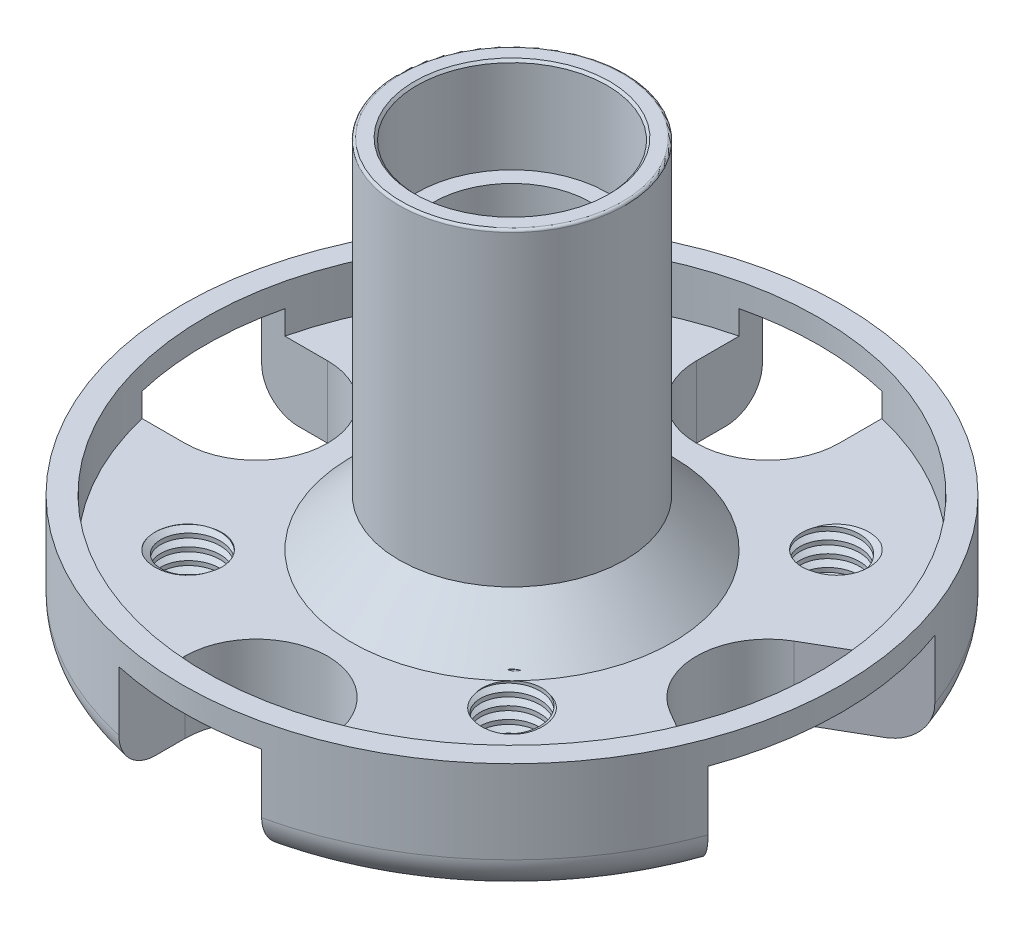
SolidWorks part; units mm, degrees
material "3003-H16"
ref_plane "Спереди" through (0, 0, 0) normal (0, 0, 1) x (1, 0, 0)
ref_plane "Сверху" through (0, 0, 0) normal (0, 1, 0) x (1, 0, 0)
ref_plane "Справа" through (0, 0, 0) normal (1, 0, 0) x (0, 0, -1)
sketch "Эскиз1" plane through (0, 0, 0) normal (0, 0, 1) x (1, 0, 0)
  line L0 (0, 0) -> (0, 55.4905) construction
  line L1 (4, 0.1) -> (4, 4)
  line L2 (4, 4) -> (3.3, 4)
  line L3 (3.3, 4) -> (3.3, 14)
  line L4 (3.3, 14) -> (4, 14)
  line L5 (4, 14) -> (4, 17.9)
  line L6 (4.1, 18) -> (4.65, 18)
  line L7 (13.85, 1.5) -> (13.85, 5)
  line L8 (13.85, 5) -> (12.9, 5)
  line L9 (12.9, 5) -> (12.9, 3)
  line L10 (12.35, 0) -> (4.1, 0)
  line L11 (4.75, 17.9) -> (4.75, 5)
  line L12 (4.75, 5) -> (6.75, 3)
  line L13 (4, 17.9) -> (4.1, 18)
  line L14 (4.1, 0) -> (4, 0.1)
  line L18 (12.9, 3) -> (6.75, 3)
  arc A0 (13.85, 1.5) -> (12.35, 0) centre (12.35, 1.5) cw
  arc A1 (4.65, 18) -> (4.75, 17.9) centre (4.65, 17.9) cw
  point P9 (4, 18)
  point P48 (4, 0)
  dimension "D12" = 1.5
  dimension "D14" = 0.1
  dimension "D1" = 6.6
  dimension "D2" = 8
  dimension "D3" = 4
  dimension "D4" = 18
  dimension "D5" = 9.5
  dimension "D6" = 45
  dimension "D7" = 3
  dimension "D8" = 13
  dimension "D9" = 27.7
  dimension "D10" = 0.95
  dimension "D11" = 5
  dimension "D13" = 3.5
  dimension "D15" = 0.1
  dimension "D16" = 45
  dimension "D17" = 4
  dimension "D18" = 0.1
  dimension "D19" = 45
revolve "Повернуть1" add sketch "Эскиз1" angle 360 about L0
sketch "Эскиз4" plane through (0, 0, 0) normal (0, -1, 0) x (1, 0, 0)
  line L0 (-3, 13.5212) -> (-3, 10.75)
  line L1 (3, 10.75) -> (3, 13.5212)
  line L2 (0, 0) -> (0, 14.6835) construction
  arc A1 (-3, 10.75) -> (3, 10.75) centre (0, 10.75) ccw
  arc A2 (3, 13.5212) -> (-3, 13.5212) centre (0, 0) ccw
  circle A3 centre (0, 0) radius 7.75 construction
  circle A4 centre (0, 0) radius 13.85 construction
  dimension "D1" = 3
  dimension "D2" = 15.5
extrude "Вырез-Вытянуть3" cut sketch "Эскиз4" against normal blind 4
pattern_circular "Круговой массив2" count 4 over 360 of "Вырез-Вытянуть3"
sketch "Эскиз5" plane through (0, 0, 0) normal (0, -1, 0) x (1, 0, 0)
  line L0 (9.25, 2.5981) -> (13.0043, 4.7656)
  line L1 (10.75, 0) -> (16.1634, 0) construction
  line L2 (9.25, -2.5981) -> (13.0043, -4.7656)
  arc A0 (10.75, 3) -> (10.75, -3) centre (10.75, 0) ccw construction
  arc A2 (9.25, 2.5981) -> (9.25, -2.5981) centre (10.75, 0) ccw
  arc A3 (13.0043, -4.7656) -> (13.0043, 4.7656) centre (0, 0) ccw
  arc A4 (3, -13.5212) -> (13.5212, -3) centre (0, 0) ccw construction
  dimension "D1" = 60
extrude "Вырез-Вытянуть4" cut sketch "Эскиз5" against normal blind 4
sketch "Эскиз14" plane through (0, 0, 0) normal (0, -1, 0) x (1, 0, 0)
  line L0 (5.6569, 5.6569) -> (-5.6569, -5.6569) construction
  line L1 (0, 0) -> (18.5147, 0) construction
  line L2 (-6.7175, 6.7175) -> (6.7175, -6.7175) construction
  circle A0 centre (0, 0) radius 8 construction
  circle A1 centre (0, 0) radius 9.5 construction
  dimension "D1" = 16
  dimension "D3" = 19
  dimension "D2" = 45
hole_wizard "Отверстие обработанное метчиком M31" positions "Эскиз16" profile "Эскиз15" tap size "M3" standard "ISO" end condition up to next
sketch "Эскиз16" plane through (0, 0, 0) normal (0, -1, 0) x (1, 0, 0)
  point P0 (-6.7175, 6.7175)
  point P3 (6.7175, -6.7175)
  point P6 (5.6569, 5.6569)
  point P9 (-5.6569, -5.6569)
sketch "Эскиз15" plane through (-6.7175, 0, 6.7175) normal (1, 0, 0) x (0, 0, -1)
  line L0 (0, 0) -> (0, 3)
  line L1 (0, 3) -> (1.25, 3)
  line L2 (1.25, 3) -> (1.25, 0.5)
  line L3 (1.25, 0.5) -> (1.75, 0)
  line L5 (1.75, 0) -> (0, 0)
  line L6 (-1.25, 0.5) -> (-1.75, 0) construction
  line L11 (0, -6.35) -> (0, 107.95) construction
  dimension "Диаметр резьбы" = 2.5
  dimension "Глубина проходного сверла" = 3
  dimension "Диаметр передней зенковки" = 3.5
  dimension "Угол передней зенковки" = 90
ref_plane "Плоскость1" through (0, 0, 0) normal (0.7071, 0, 0.7071) x (0.7071, 0, -0.7071)
sketch "Эскиз17" plane through (0, 0, 0) normal (0, -1, 0) x (1, 0, 0)
  circle A0 centre (6.7175, -6.7175) radius 1.5
  dimension "D1" = 3
curve "Спираль1" pitch 0.5 height 3.5 radius 1.5 centre (6.7175, 0, -6.7175) axis (0, 1, 0) start towards (0.7071, 0, -0.7071)
sketch "Эскиз18" plane through (0, 0, 0) normal (0.7071, 0, 0.7071) x (0.7071, 0, -0.7071)
  line L0 (11, -0.0156) -> (11, 0.0156)
  line L1 (11, 0.0156) -> (10.6482, 0.2187)
  line L2 (10.6482, 0.2187) -> (10.6482, 0.25)
  line L3 (10.6482, 0.25) -> (10.5482, 0.25)
  line L4 (10.5482, 0.25) -> (10.5482, -0.25)
  line L5 (10.5482, -0.25) -> (10.6482, -0.25)
  line L6 (10.6482, -0.25) -> (10.6482, -0.2188)
  line L7 (10.6482, -0.2188) -> (11, -0.0156)
  line L8 (11, 0) -> (10.0705, 0) construction
  line L9 (7.75, 0) -> (11.25, 0) construction
  point P2 (11, 0)
  dimension "D1" = 0.5
  dimension "D2" = 60
  dimension "D3" = 0.0312
  dimension "D4" = 0.0312
  dimension "D5" = 0.1
sweep "Вырез-По траектории1" cut profiles "Эскиз18" path "Спираль1" align with end faces yes
pattern_circular "Круговой массив3" count 2 over 360 of "Вырез-По траектории1"
ref_plane "Плоскость2" through (0, 0, 0) normal (-0.7071, 0, 0.7071) x (0.7071, 0, 0.7071)
sketch "Эскиз19" plane through (0, 0, 0) normal (0, -1, 0) x (1, 0, 0)
  circle A0 centre (5.6569, 5.6569) radius 1.5
  dimension "D1" = 3
curve "Спираль2" pitch 0.5 height 3.5 radius 1.5 centre (5.6569, 0, 5.6569) axis (0, 1, 0) start towards (0.7071, 0, 0.7071)
sketch "Эскиз20" plane through (0, 0, 0) normal (-0.7071, 0, 0.7071) x (0.7071, 0, 0.7071)
  line L0 (9.5, -0.0156) -> (9.5, 0.0156)
  line L1 (9.5, 0.0156) -> (9.1482, 0.2188)
  line L2 (9.1482, 0.2188) -> (9.1482, 0.25)
  line L3 (9.1482, 0.25) -> (9.0482, 0.25)
  line L4 (9.0482, 0.25) -> (9.0482, -0.25)
  line L5 (9.0482, -0.25) -> (9.1482, -0.25)
  line L6 (9.1482, -0.25) -> (9.1482, -0.2188)
  line L7 (9.1482, -0.2188) -> (9.5, -0.0156)
  line L8 (9.5, 0) -> (8.7964, 0) construction
  point P2 (9.5, 0)
  dimension "D1" = 0.5
  dimension "D2" = 60
  dimension "D3" = 0.0312
  dimension "D4" = 0.0312
  dimension "D5" = 0.1
sweep "Вырез-По траектории2" cut profiles "Эскиз20" path "Спираль2" align with end faces yes
pattern_circular "Круговой массив4" count 2 over 360 of "Вырез-По траектории2"
